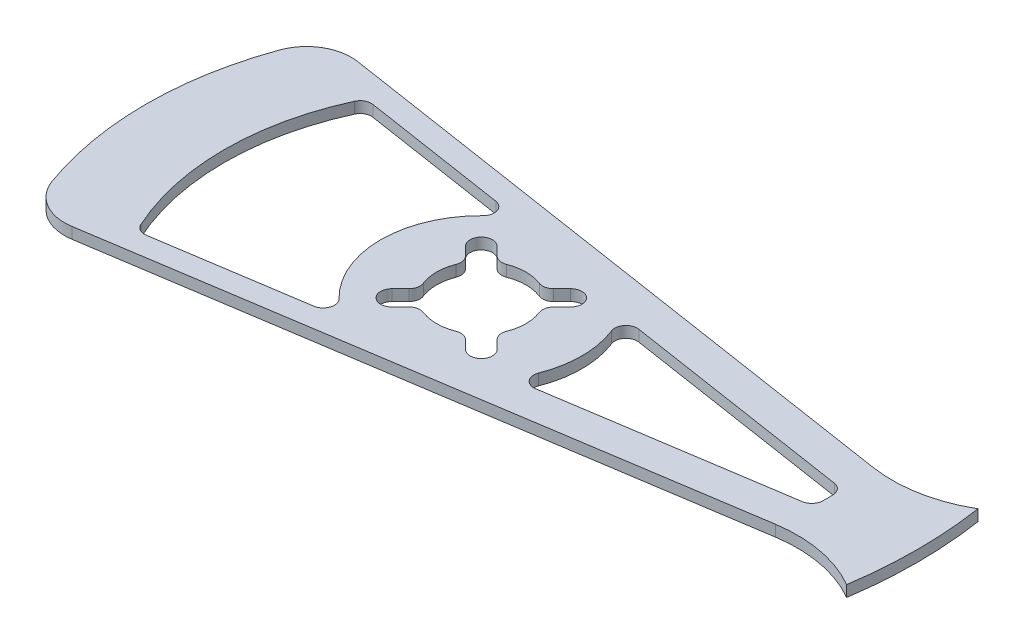
SolidWorks part; units mm, degrees
material "AISI 4340 Steel, normalized"
ref_plane "Front Plane" through (0, 0, 0) normal (0, 0, 1) x (1, 0, 0)
ref_plane "Top Plane" through (0, 0, 0) normal (0, 1, 0) x (1, 0, 0)
ref_plane "Right Plane" through (0, 0, 0) normal (1, 0, 0) x (0, 0, -1)
other "Center of Mass"
sketch "Sketch1" plane through (0, 0, 0) normal (0, 1, 0) x (1, 0, 0)
  line L0 (-170.9166, 84.1295) -> (194.8729, 27.8292)
  line L1 (-170.9166, -84.1295) -> (194.8729, -27.8292)
  line L2 (-130.6087, 65.076) -> (-28.7411, 49.3971)
  line L3 (-130.6087, -65.076) -> (-28.7411, -49.3971)
  line L4 (47.8972, 31.1766) -> (196.6759, 8.2773)
  line L5 (47.8972, -31.1766) -> (196.6759, -8.2773)
  line L6 (-29.8901, 20.9099) -> (-21.8803, 12.9001)
  line L7 (-25.4, -25.4) -> (25.4, -25.4) construction
  line L8 (-25.4, -25.4) -> (-25.4, 25.4) construction
  line L9 (-25.4, 25.4) -> (25.4, 25.4) construction
  line L10 (25.4, -25.4) -> (25.4, 25.4) construction
  line L11 (-25.4, -25.4) -> (25.4, 25.4) construction
  line L12 (-25.4, 25.4) -> (25.4, -25.4) construction
  line L13 (-20.9099, 29.8901) -> (-12.9001, 21.8803)
  line L14 (29.8901, 20.9099) -> (21.8803, 12.9001)
  line L15 (20.9099, 29.8901) -> (12.9001, 21.8803)
  line L16 (20.9099, -29.8901) -> (12.9001, -21.8803)
  line L17 (29.8901, -20.9099) -> (21.8803, -12.9001)
  line L18 (-29.8901, -20.9099) -> (-21.8803, -12.9001)
  line L19 (-20.9099, -29.8901) -> (-12.9001, -21.8803)
  line L20 (0, 0) -> (244.8246, 37.3019) construction
  circle A0 centre (0, 0) radius 57.15 construction
  circle A1 centre (0, 0) radius 247.65 construction
  arc A2 (244.8246, 37.3019) -> (244.8246, -37.3019) centre (0, 0) cw
  arc A3 (194.8729, -27.8292) -> (244.8246, -37.3019) centre (206.4647, -103.1423) cw
  arc A4 (194.8729, 27.8292) -> (244.8246, 37.3019) centre (206.4647, 103.1423) ccw
  circle A5 centre (0, 0) radius 190.5 construction
  arc A6 (-170.9166, 84.1295) -> (-170.9166, -84.1295) centre (0, 0) ccw
  circle A7 centre (0, 0) radius 196.85 construction
  circle A8 centre (0, 0) radius 145.923 construction
  arc A9 (-130.6087, 65.076) -> (-130.6087, -65.076) centre (0, 0) ccw
  arc A10 (-28.7411, 49.3971) -> (-28.7411, -49.3971) centre (0, 0) ccw
  arc A11 (47.8972, 31.1766) -> (47.8972, -31.1766) centre (0, 0) cw
  arc A12 (196.6759, 8.2773) -> (196.6759, -8.2773) centre (0, 0) cw
  circle A13 centre (0, 0) radius 25.4
  circle A14 centre (-25.4, 25.4) radius 6.35
  circle A15 centre (25.4, 25.4) radius 6.35
  circle A16 centre (25.4, -25.4) radius 6.35
  circle A17 centre (-25.4, -25.4) radius 6.35
  point P18 (-190.5, 0)
  point P59 (0, 0)
  dimension "D1" = 495.3
  dimension "D2" = 50.8
  dimension "D3" = 17.5
  dimension "D4" = 114.3
  dimension "D5" = 57.15
  dimension "D6" = 76.2
  dimension "D9" = 44.577
  dimension "D12" = 50.8
  dimension "D14" = 12.7
  dimension "D15" = 4
  dimension "D7" = 12.7
  dimension "D8" = 12.7
  dimension "D10" = 19.05
  dimension "D11" = 19.05
  dimension "D13" = 50.8
extrude "Boss-Extrude1" add sketch "Sketch1" along normal blind 6.35 contours L0 A6 L1 A3 A2 A4 L2 A10 L3 A9 region at (11.2642, 0, -51.3405)
fillet "Fillet1" radius 6.35 8 edges at (47.8972, 3.175, 31.1766) (47.8972, 3.175, -31.1766) (196.6759, 3.175, -8.2773) (196.6759, 3.175, 8.2773) (-130.6087, 3.175, -65.076) (-130.6087, 3.175, 65.076) (-28.7411, 3.175, -49.3971) (-28.7411, 3.175, 49.3971)
fillet "Fillet2" radius 25.4 2 edges at (-170.9166, 3.175, -84.1295) (-170.9166, 3.175, 84.1295)
fillet "Fillet3" radius 6.35 8 edges at (-12.9001, 3.175, 21.8803) (12.9001, 3.175, 21.8803) (21.8803, 3.175, 12.9001) (21.8803, 3.175, -12.9001) (-12.9001, 3.175, -21.8803) (12.9001, 3.175, -21.8803) (-21.8803, 3.175, -12.9001) (-21.8803, 3.175, 12.9001)
